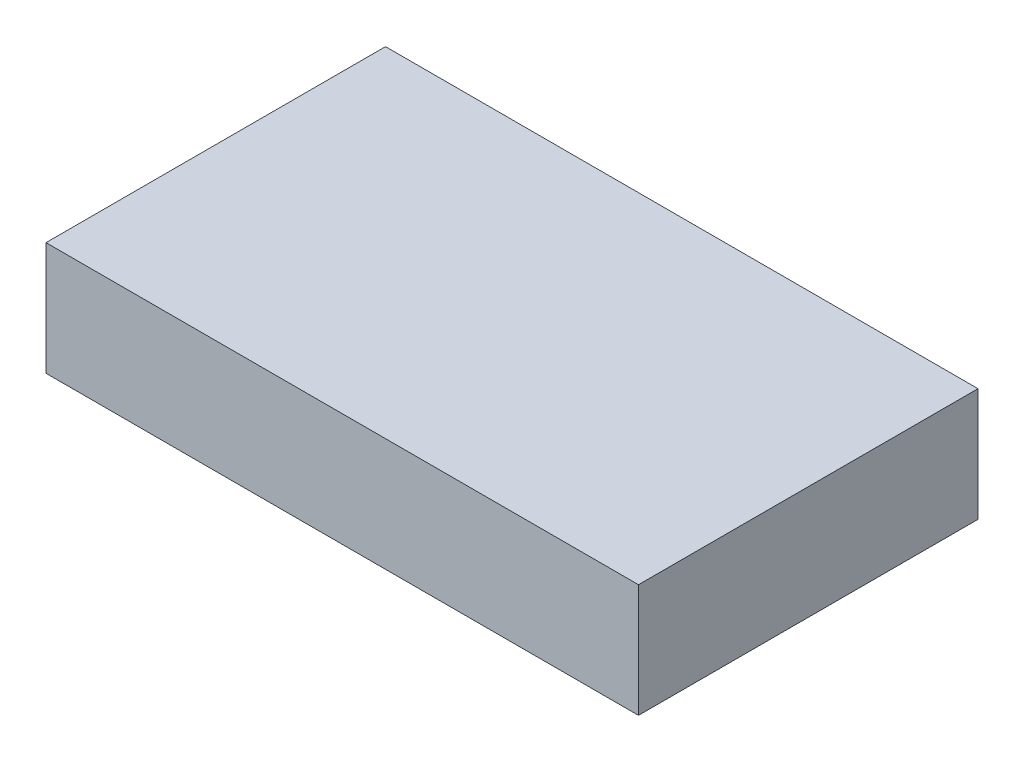
SolidWorks part; units mm, degrees
ref_plane "Alzado" through (0, 0, 0) normal (0, 0, 1) x (1, 0, 0)
ref_plane "Planta" through (0, 0, 0) normal (0, 1, 0) x (1, 0, 0)
ref_plane "Vista lateral" through (0, 0, 0) normal (1, 0, 0) x (0, 0, -1)
sketch "Croquis1" plane through (0, 0, 0) normal (0, 1, 0) x (1, 0, 0)
  line L1 (44.5, 25.5) -> (-44.5, 25.5)
  line L2 (44.5, 25.5) -> (44.5, -25.5)
  line L3 (44.5, -25.5) -> (-44.5, -25.5)
  line L4 (-44.5, 25.5) -> (-44.5, -25.5)
  line L5 (44.5, 25.5) -> (-44.5, -25.5) construction
  line L6 (44.5, -25.5) -> (-44.5, 25.5) construction
  point P0 (0, 0)
  dimension "D1" = 89
  dimension "D2" = 51
extrude "Saliente-Extruir1" add sketch "Croquis1" along normal blind 4.6
sketch "Croquis2" plane through (0, 4.6, 0) normal (0, 1, 0) x (1, 0, 0)
  line L4 (-44.5, 25.5) -> (-44.5, -25.5)
  line L5 (-44.5, -25.5) -> (44.5, -25.5)
  line L6 (44.5, -25.5) -> (44.5, 25.5)
  line L7 (44.5, 25.5) -> (-44.5, 25.5)
  line L8 (-44.5, 25.5) -> (-44.5, -25.5)
  line L9 (-44.5, -25.5) -> (44.5, -25.5)
  line L10 (44.5, -25.5) -> (44.5, 25.5)
  line L11 (44.5, 25.5) -> (-44.5, 25.5)
  dimension "D1" = 0
extrude "Saliente-Extruir2" add sketch "Croquis2" along normal blind 12.4
